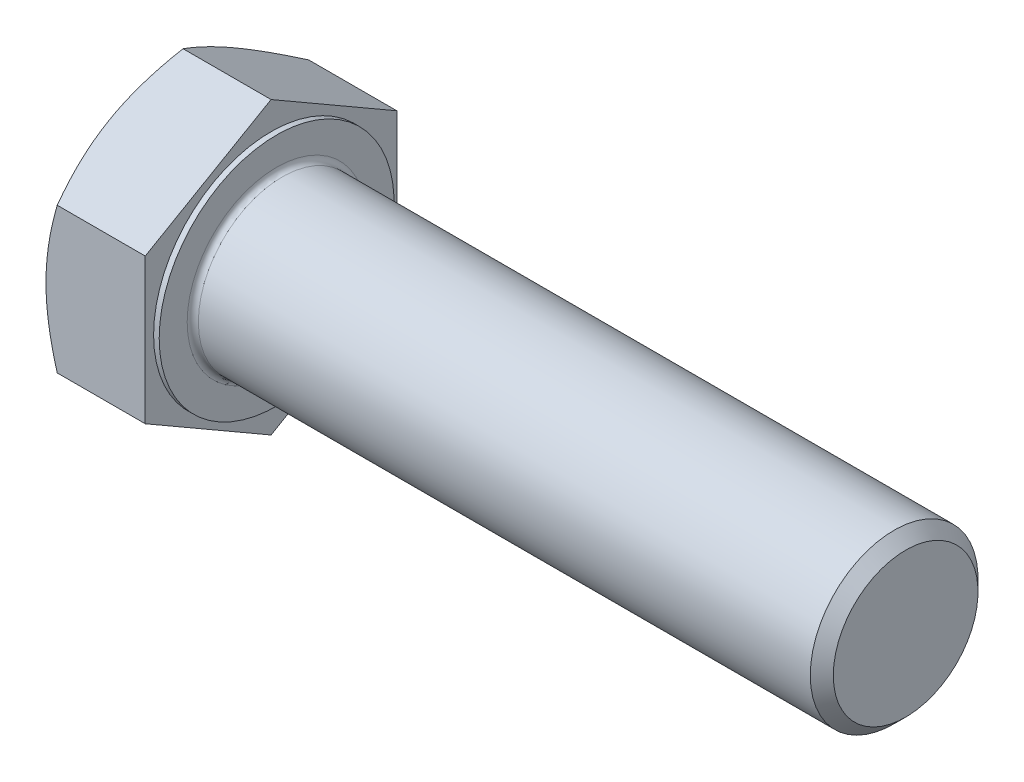
SolidWorks part; units mm, degrees
ref_plane "Front Plane" through (0, 0, 0) normal (0, 0, 1) x (1, 0, 0)
ref_plane "Top Plane" through (0, 0, 0) normal (0, 1, 0) x (1, 0, 0)
ref_plane "Right Plane" through (0, 0, 0) normal (1, 0, 0) x (0, 0, -1)
sketch "BaseHeadSke" plane through (0, 0, 0) normal (1, 0, 0) x (0, 0, -1)
  line L1 (18, 10.3923) -> (0, 20.7846)
  line L2 (0, 20.7846) -> (-18, 10.3923)
  line L3 (-18, 10.3923) -> (-18, -10.3923)
  line L4 (-18, -10.3923) -> (0, -20.7846)
  line L5 (0, -20.7846) -> (18, -10.3923)
  line L6 (18, -10.3923) -> (18, 10.3923)
  circle A0 centre (0, 0) radius 18 construction
extrude "BaseHead" add sketch "BaseHeadSke" along normal blind 15
sketch "BodySke" plane through (0, 0, 0) normal (0, 0, 1) x (1, 0, 0)
  line L0 (0, 0) -> (105, 0)
  line L1 (105, 0) -> (105, 10.352)
  line L2 (105, 10.352) -> (103.352, 12)
  line L3 (103.352, 12) -> (0, 12)
  line L4 (0, 12) -> (0, 0)
  line L5 (15, 10.3923) -> (15, -10.3923) construction
  line L6 (0, 0) -> (159.3976, 0) construction
  line L7 (51, -84.3176) -> (51, 77.7215) construction
  line L8 (102, -21.5941) -> (102, 39.2994) construction
  dimension "Thread_length" = 54
  dimension "Advance" = 3
revolve "BaseBody" add sketch "BodySke" angle 360 about L6
cosmetic thread "ThreadCosmetic" [suppressed] parameters "Thread_length"=54, "Thread_minor"=20.704
sketch "HeadChamferSke" plane through (0, 0, 0) normal (0, 0, 1) x (1, 0, 0)
  line L0 (1.6077, 20.7846) -> (0, 20.7846)
  line L1 (0, 20.7846) -> (0, 18)
  line L2 (0, 18) -> (1.6077, 20.7846)
  line L3 (0, 0) -> (120.9185, 0) construction
  dimension "D1" = 30
revolve "HeadChamfer" cut sketch "HeadChamferSke" angle 360 about L3
sketch "BearingFaceSke" plane through (0, 0, 0) normal (0, 0, 1) x (1, 0, 0)
  line L0 (0, 0) -> (129.6443, 0) construction
  line L1 (14.2, 20.7846) -> (15, 20.7846)
  line L2 (14.2, 20.7846) -> (14.2, 16.805)
  line L3 (14.2, 16.805) -> (15, 16.805)
  line L4 (15, 20.7846) -> (15, 16.805)
  dimension "Bearing_height" = 0.8
  dimension "Dw" = 33.61
revolve "BearingFace" cut sketch "BearingFaceSke" angle 360 about L0
fillet "Fillet" radius 0.8 1 edges at (15, 0, 12)
sketch "ThdSchSke" plane through (0, 0, 0) normal (0, 0, 1) x (1, 0, 0)
  line L0 (101.0485, 13.9029) -> (101.0485, 12)
  line L1 (101.0485, 12) -> (102, 10.352)
  line L2 (102, 10.352) -> (102.9515, 12)
  line L3 (102.9515, 12) -> (102.9515, 13.9029)
  line L4 (102.9515, 13.9029) -> (101.0485, 13.9029)
  line L6 (0, 0) -> (141.9934, 0) construction
  line L7 (105, -10.352) -> (105, 10.352) construction
  dimension "D2" = 20.704
  dimension "D3" = 24
  dimension "Advance" = 3
revolve "ThreadSchematic" [suppressed] cut sketch "ThdSchSke" angle 360 about L6
pattern_linear "ThdSchPat" [suppressed] count 17 spacing 3 along (-1, 0, 0) of bodies 107
equation "\"Thread_minor@ThreadCosmetic\" = \"Minor_dia@BodySke\""
equation "\"Thread_length@ThreadCosmetic\" = \"Thread_length@BodySke\""
equation "\"Head_chamfer@HeadChamferSke\" = \"Width_flats@BaseHeadSke\""
equation "\"D2@ThdSchSke\" = \"Minor_dia@BodySke\""
equation "\"D3@ThdSchSke\" = \"Diameter@BodySke\""
equation "\"Advance@ThdSchSke\" = \"Advance@BodySke\""
equation "\"D3@ThdSchPat\" = \"Advance@BodySke\""
equation "\"D1@ThdSchPat\" =  int( \"Thread_length@BodySke\"/\"Advance@BodySke\" )-1"
